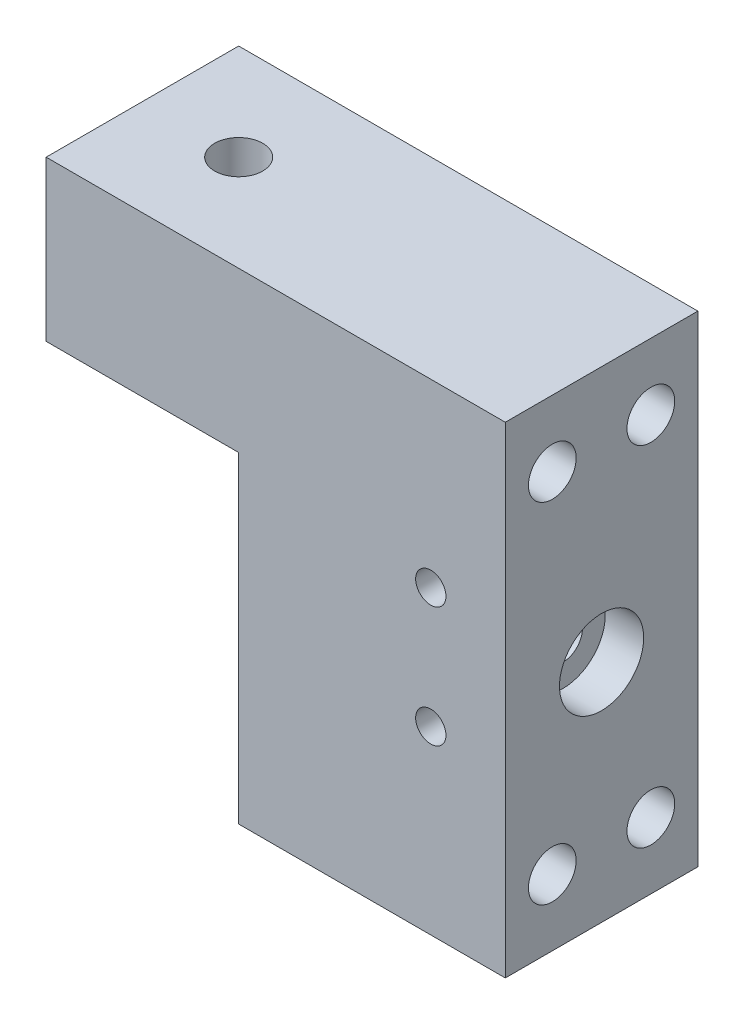
SolidWorks part; units mm, degrees
material "McMaster 6061-T6"
ref_plane "Front Plane" through (0, 0, 0) normal (0, 0, 1) x (1, 0, 0)
ref_plane "Top Plane" through (0, 0, 0) normal (0, 1, 0) x (1, 0, 0)
ref_plane "Right Plane" through (0, 0, 0) normal (1, 0, 0) x (0, 0, -1)
sketch "Sketch2" plane through (0, 0, 0) normal (1, 0, 0) x (0, 0, -1)
  line L1 (-212.3494, -348.1117) -> (-237.7494, -348.1117)
  line L2 (-212.3494, -348.1117) -> (-212.3494, -411.6117)
  line L3 (-212.3494, -411.6117) -> (-237.7494, -411.6117)
  line L4 (-237.7494, -348.1117) -> (-237.7494, -411.6117)
  dimension "D1" = 25.4
  dimension "D2" = 63.5
extrude "Boss-Extrude1" add sketch "Sketch2" against normal up to surface (35.176 mm away)
sketch "Sketch3" plane through (-35.176, 0, 0) normal (-1, 0, 0) x (0, 0, 1)
  line L0 (212.3494, -348.1117) -> (212.3494, -411.6117) construction
  line L1 (237.7494, -348.1117) -> (212.3494, -348.1117)
  line L2 (237.7494, -348.1117) -> (237.7494, -369.1617)
  line L3 (237.7494, -369.1617) -> (212.3494, -369.1617)
  line L4 (212.3494, -348.1117) -> (212.3494, -369.1617)
  line L5 (-121.6612, -369.1617) -> (707.4994, -369.1617) construction
extrude "Boss-Extrude2" add sketch "Sketch3" along normal blind 25.4
sketch "Sketch6" plane through (0, -348.1117, 0) normal (0, 1, 0) x (1, 0, 0)
  line L0 (-47.876, -237.7494) -> (-47.876, -212.3494) construction
  line L1 (-60.576, -237.7494) -> (0, -237.7494) construction
  line L2 (-60.576, -212.3494) -> (0, -212.3494) construction
  line L3 (-60.576, -237.7494) -> (-60.576, -212.3494) construction
  point P8 (-47.876, -225.0494)
  dimension "D1" = 12.7
hole_wizard "1/4 (0.25) Diameter Hole1" positions "Sketch7" profile "Sketch9" hole size "1/4" standard "ANSI Inch" end condition through all
sketch "Sketch7" plane through (0, -348.1117, 0) normal (0, 1, 0) x (1, 0, 0)
  point P0 (-47.876, -225.0494)
sketch "Sketch9" plane through (-47.876, -348.1117, 225.0494) normal (1, 0, 0) x (0, 0, 1)
  line L0 (0, 0) -> (0, 63.5)
  line L1 (0, 63.5) -> (3.175, 63.5)
  line L2 (3.175, 63.5) -> (3.175, 0)
  line L5 (3.175, 0) -> (0, 0)
  line L11 (0, -6.35) -> (0, 107.95) construction
  dimension "Thru Hole Dia." = 6.35
  dimension "Thru Hole Depth" = 63.5
hole_wizard "Ø1.0mm Dowel Hole1" positions "Sketch12" profile "Sketch13" hole size "Ø1.0" standard "ANSI Metric"
sketch "Sketch12" plane through (0, 0, 0) normal (1, 0, 0) x (0, 0, -1)
  circle A0 centre (-218.5494, -402.8617) radius 2.4455 construction
  point P0 (-231.5494, -356.8617)
  point P3 (-218.5494, -356.8617)
  point P6 (-231.5494, -402.8617)
  point P9 (-218.5494, -402.8617)
sketch "Sketch13" plane through (0, -356.8617, 231.5494) normal (0, 1, 0) x (0, 0, -1)
  line L0 (0, 0) -> (0, 10.8843)
  line L1 (0, 10.8843) -> (3.15, 8.9916)
  line L2 (3.15, 8.9916) -> (3.15, 0)
  line L5 (3.15, 0) -> (0, 0)
  line L10 (0, 10.8843) -> (-3.15, 8.9916) construction
  line L11 (0, -6.35) -> (0, 107.95) construction
  dimension "Hole Dia." = 6.3
  dimension "Hole Depth" = 8.9916
  dimension "Drill Angle" = 118
hole_wizard "Ø4.0mm Dowel Hole1" positions "Sketch14" profile "Sketch15" hole size "Ø4.0" standard "ANSI Metric"
sketch "Sketch14" plane through (0, 0, 237.7494) normal (0, 0, -1) x (-1, 0, 0)
  point P0 (9.8313, -371.9242)
  point P3 (9.8313, -387.7992)
sketch "Sketch15" plane through (-9.8313, -371.9242, 237.7494) normal (1, 0, 0) x (0, -1, 0)
  line L0 (0, 0) -> (0, 16.4417)
  line L1 (0, 16.4417) -> (2, 15.24)
  line L2 (2, 15.24) -> (2, 0)
  line L5 (2, 0) -> (0, 0)
  line L10 (0, 16.4417) -> (-2, 15.24) construction
  line L11 (0, -6.35) -> (0, 107.95) construction
  dimension "Hole Dia." = 4
  dimension "Hole Depth" = 15.24
  dimension "Drill Angle" = 118
hole_wizard "CBORE for #10 Binding Head Machine Screw1" positions "Sketch17" profile "Sketch18" counterbore size "#10" standard "ANSI Inch" end condition up to next
sketch "Sketch17" plane through (0, 0, 0) normal (1, 0, 0) x (0, 0, -1)
  line L0 (-212.3494, -381.8617) -> (-237.7494, -381.8617) construction
  line L1 (-212.3494, -411.6117) -> (-212.3494, -348.1117) construction
  line L2 (-237.7494, -348.1117) -> (-237.7494, -411.6117) construction
  point P0 (-225.0494, -381.8617)
sketch "Sketch18" plane through (0, -381.8617, 225.0494) normal (0, 1, 0) x (0, 0, -1)
  line L0 (0, 0) -> (0, 35.176)
  line L1 (0, 35.176) -> (2.5527, 35.176)
  line L3 (2.5527, 35.176) -> (2.5527, 5.08)
  line L4 (2.5527, 5.08) -> (5.5562, 5.08)
  line L5 (5.5562, 5.08) -> (5.5562, 0)
  line L7 (5.5562, 0) -> (0, 0)
  line L11 (0, -6.35) -> (0, 107.95) construction
  dimension "Thru Hole Dia." = 5.1054
  dimension "Thru Hole Depth" = 35.176
  dimension "C'Bore Dia." = 11.1125
  dimension "C'Bore Depth" = 5.08
